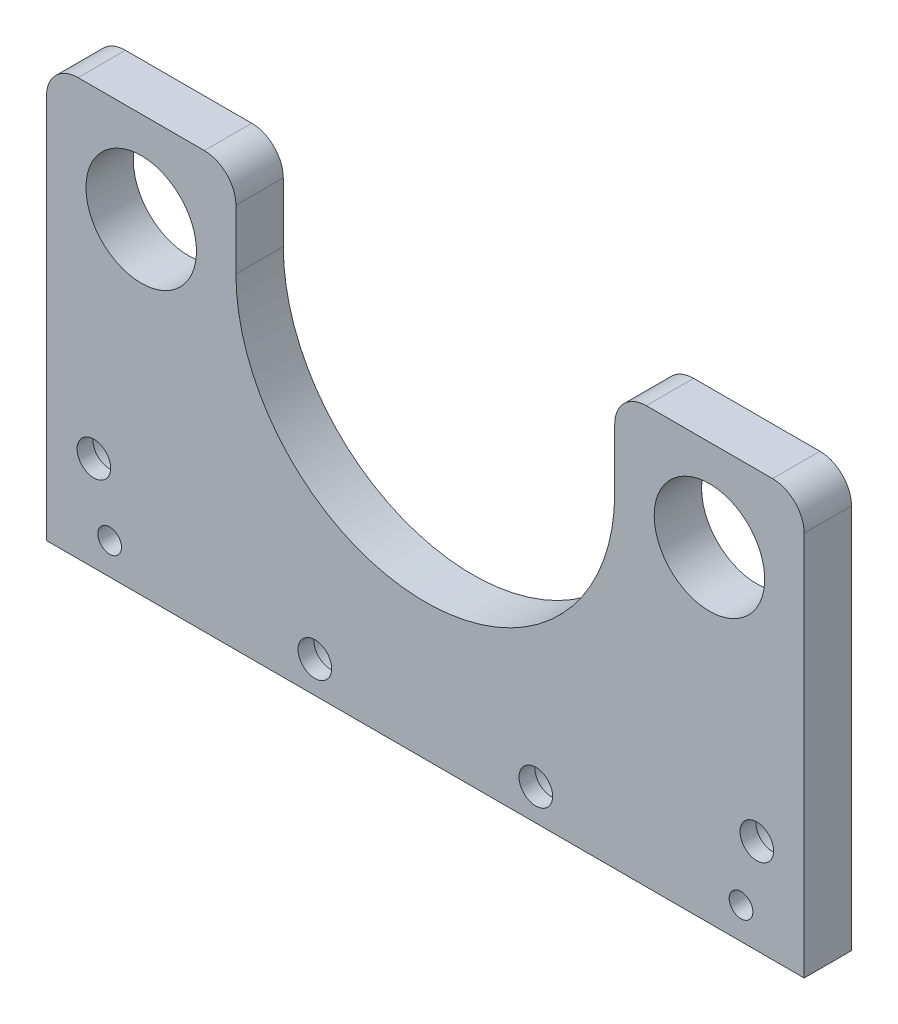
SolidWorks part; units mm, degrees
material "6061 Alloy"
ref_plane "Front" through (0, 0, 0) normal (0, 0, 1) x (1, 0, 0)
ref_plane "Top" through (0, 0, 0) normal (0, 1, 0) x (1, 0, 0)
ref_plane "Right" through (0, 0, 0) normal (1, 0, 0) x (0, 0, -1)
ref_axis "Axis" through (0, 0, -80.9) along (0, 0, 1)
sketch "Sketch1" plane through (0, 0, 0) normal (0, 0, 1) x (1, 0, 0)
  line L0 (0, -65.4837) -> (0, 0) construction
  line L1 (76.2, 11.9863) -> (76.2, -65.4837)
  line L2 (57.15, 0) -> (-57.15, 0) construction
  line L3 (38.1, 0) -> (38.1, 11.9863)
  line L4 (-38.1, 0) -> (-38.1, 11.9863)
  line L5 (69.85, 18.3363) -> (44.45, 18.3363)
  line L6 (-69.85, 18.3363) -> (-44.45, 18.3363)
  line L31 (76.2, -65.4837) -> (-76.2, -65.4837)
  line L34 (-76.2, 11.9863) -> (-76.2, -65.4837)
  arc A0 (-44.45, 18.3363) -> (-38.1, 11.9863) centre (-44.45, 11.9863) cw
  circle A1 centre (-57.15, 0) radius 11.1125
  circle A2 centre (57.15, 0) radius 11.1125
  arc A3 (76.2, 11.9863) -> (69.85, 18.3363) centre (69.85, 11.9863) ccw
  arc A4 (44.45, 18.3363) -> (38.1, 11.9863) centre (44.45, 11.9863) ccw
  arc A5 (-76.2, 11.9863) -> (-69.85, 18.3363) centre (-69.85, 11.9863) cw
  arc A6 (-38.1, 0) -> (38.1, 0) centre (0, 0) ccw
  dimension "D2" = 22.225
  dimension "D3" = 83.82
  dimension "D5" = 38.1
  dimension "D7" = 6.35
  dimension "D4" = 65.4837
  dimension "D6" = 152.4
  dimension "D10" = 114.3
extrude "Base" add sketch "Sketch1" along normal mid plane 9.525
hole_wizard "1/4 Cap screw carriage mounts" positions "Sketch6" profile "Sketch5" counterbore size "1/4" standard "Ansi Inch" end condition through all
sketch "Sketch6" plane through (-61.9874, 5.4091, -4.7625) normal (0, 0, 1) x (1, 0, 0)
  line L2 (84.2124, -64.5428) -> (39.7624, -64.5428) construction
  line L3 (39.7624, -64.5428) -> (-4.6876, -64.5428) construction
  line L4 (84.2124, -64.5428) -> (128.6624, -64.5428) construction
  line L5 (61.9874, -5.4091) -> (61.9874, -64.5428) construction
  line L7 (-14.2126, -70.8928) -> (138.1874, -70.8928) construction
  point P0 (-4.6876, -51.8428)
  point P1 (39.7624, -64.5428)
  point P3 (128.6624, -51.8428)
  point P5 (84.2124, -64.5428)
  dimension "D2" = 19.05
  dimension "D3" = 6.35
  dimension "D5" = 44.45
sketch "Sketch5" plane through (-66.675, -46.4337, -4.7625) normal (1, 0, 0) x (0, 1, 0)
  line L0 (0, 0) -> (0, 9.525)
  line L1 (0, 9.525) -> (3.3782, 9.525)
  line L3 (3.3782, 9.525) -> (3.3782, 6.35)
  line L4 (3.3782, 6.35) -> (5.5562, 6.35)
  line L5 (5.5562, 6.35) -> (5.5562, 0)
  line L7 (5.5562, 0) -> (0, 0)
  line L11 (0, -6.35) -> (0, 107.95) construction
  dimension "Thru Hole Dia." = 6.7564
  dimension "Thru Hole Depth" = 9.525
  dimension "C'Bore Dia." = 11.1125
  dimension "C'Bore Depth" = 6.35
sketch "Sketch8" plane through (0, 0, -4.7625) normal (0, 0, -1) x (-1, 0, 0)
  line L0 (76.2, -65.4837) -> (-76.2, -65.4837) construction
  line L1 (64.262, -65.4837) -> (39.751, -65.4837)
  line L2 (64.262, -65.4837) -> (64.262, -64.9757)
  line L3 (64.262, -64.9757) -> (39.751, -64.9757)
  line L4 (39.751, -65.4837) -> (39.751, -64.9757)
  line L5 (0, -65.4837) -> (0, 0) construction
  line L6 (76.2, 11.9863) -> (76.2, -65.4837) construction
  line L7 (-39.751, -65.4837) -> (-39.751, -64.9757)
  line L8 (-64.262, -64.9757) -> (-39.751, -64.9757)
  line L9 (-64.262, -65.4837) -> (-64.262, -64.9757)
  line L10 (-64.262, -65.4837) -> (-39.751, -65.4837)
  line L11 (-76.2, -65.4837) -> (-76.2, -64.9757)
  line L12 (73.025, -65.4837) -> (76.2, -65.4837)
  line L13 (73.025, -65.4837) -> (73.025, -64.9757)
  line L14 (73.025, -64.9757) -> (76.2, -64.9757)
  line L15 (76.2, -65.4837) -> (76.2, -64.9757)
  line L16 (-73.025, -64.9757) -> (-76.2, -64.9757)
  line L17 (-73.025, -65.4837) -> (-73.025, -64.9757)
  line L18 (-73.025, -65.4837) -> (-76.2, -65.4837)
  dimension "D1" = 11.938
  dimension "D2" = 36.449
  dimension "D3" = 0.508
  dimension "D4" = 3.175
extrude "Misc. cut" [suppressed] cut sketch "Sketch8" against normal through all
fillet "Top edge safety fillet" [suppressed] radius 1.5875
sketch "Sketch9" plane through (0, 0, 4.7625) normal (0, 0, -1) x (-1, 0, 0)
  line L0 (0, 0) -> (0, -104.4847) construction
  line L1 (-62.7062, -59.1337) -> (-64.2937, -59.1337) construction
  line L2 (-62.7062, -61.515) -> (-64.2937, -61.515) construction
  line L3 (-62.7062, -56.7525) -> (-64.2937, -56.7525) construction
  circle A0 centre (63.5, -59.1337) radius 2.3813
  circle A1 centre (-63.5, -59.1337) radius 2.3812
  arc A2 (-62.7062, -61.515) -> (-62.7062, -56.7525) centre (-62.7062, -59.1337) ccw construction
  arc A3 (-64.2937, -56.7525) -> (-64.2937, -61.515) centre (-64.2937, -59.1337) ccw construction
  point P9 (-63.5, -59.1337)
  dimension "D1" = 4.7625
  dimension "D2" = 127
  dimension "D3" = 1.5875
extrude "Alignment_pin_holes" cut sketch "Sketch9" along normal blind 6.35
